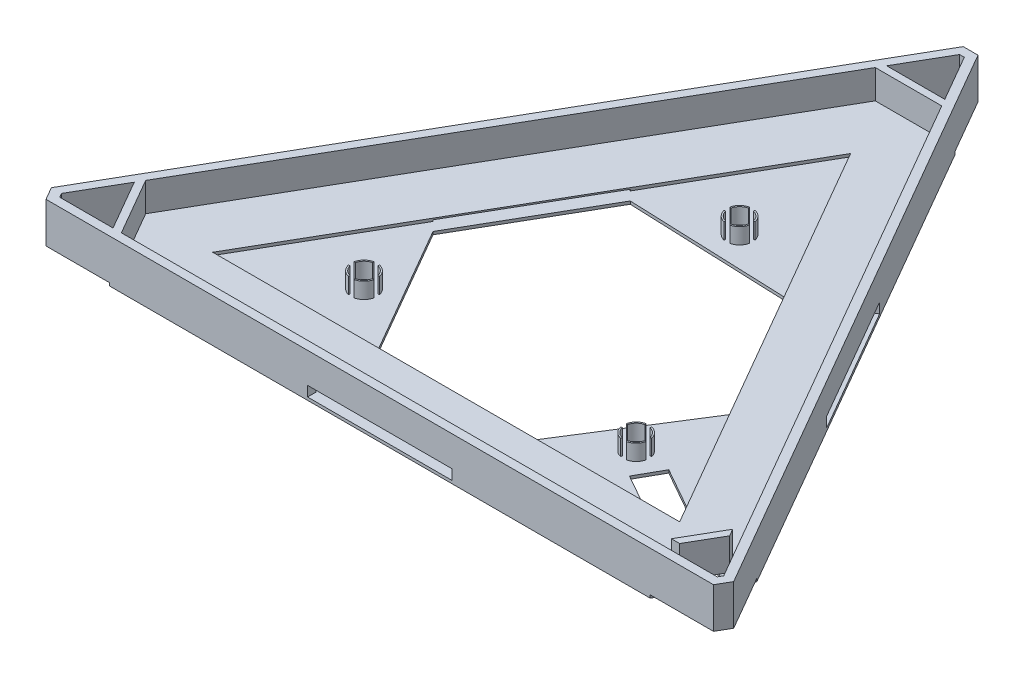
SolidWorks part; units mm, degrees
ref_plane "Front Plane" through (0, 0, 0) normal (0, 0, 1) x (1, 0, 0)
ref_plane "Top Plane" through (0, 0, 0) normal (0, 1, 0) x (1, 0, 0)
ref_plane "Right Plane" through (0, 0, 0) normal (1, 0, 0) x (0, 0, -1)
sketch "Sketch1" plane through (0, 0, 0) normal (0, 1, 0) x (1, 0, 0)
  line L0 (351.2729, 67.6655) -> (468.273, -134.9846)
  line L1 (347.2728, 67.6655) -> (347.2728, 65.1655) construction
  line L2 (409.773, -33.6595) -> (407.6079, -34.9095) construction
  line L3 (468.273, -134.9846) -> (464.2732, -141.9124)
  line L4 (230.2733, -141.9124) -> (464.2732, -141.9124)
  line L5 (230.2733, -141.9124) -> (226.2727, -134.9842)
  line L6 (226.2727, -134.9842) -> (343.2728, 67.6655)
  line L7 (353.4142, 63.9567) -> (351.2491, 62.7067) construction
  line L8 (347.2733, -141.9124) -> (347.2733, -139.4124) construction
  line L9 (231.7167, -139.4124) -> (462.8299, -139.4124)
  line L10 (284.7727, -33.6594) -> (286.9378, -34.9094) construction
  line L11 (344.7161, 65.1655) -> (349.8295, 65.1655)
  line L12 (465.3862, -134.9846) -> (349.8295, 65.1655)
  line L13 (466.2731, -138.4485) -> (464.1081, -137.1985) construction
  line L14 (462.8299, -139.4124) -> (465.3862, -134.9846)
  line L15 (229.1594, -134.9842) -> (344.7161, 65.1655)
  line L16 (229.1594, -134.9842) -> (231.7167, -139.4124)
  line L17 (286.9378, -34.9094) -> (287.3708, -35.1594) construction
  line L18 (230.438, -137.1983) -> (230.871, -136.9483) construction
  line L19 (232.0053, -138.9123) -> (229.7368, -134.9842)
  line L20 (343.2728, 67.6655) -> (351.2729, 67.6655)
  line L21 (345.0048, 64.6655) -> (229.7368, -134.9842)
  line L22 (349.5409, 64.6655) -> (345.0048, 64.6655)
  line L23 (249.0568, -126.4468) -> (246.8918, -127.697) construction
  line L24 (407.6079, -34.9095) -> (407.1749, -35.1595) construction
  line L26 (233.4463, -136.4089) -> (251.9226, -136.4093)
  line L27 (464.8089, -134.9846) -> (462.5412, -138.9123)
  line L28 (462.5412, -138.9123) -> (232.0053, -138.9123)
  line L29 (251.9226, -136.4093) -> (241.8609, -118.9847)
  line L30 (241.8609, -118.9847) -> (232.6236, -134.9842)
  line L31 (232.6236, -134.9842) -> (233.4463, -136.4089)
  line L33 (287.3708, -35.1594) -> (289.5359, -36.4094) construction
  line L34 (254.8093, -136.4089) -> (243.3042, -116.4848)
  line L35 (335.7675, 43.666) -> (243.3042, -116.4848)
  line L36 (358.7782, 43.666) -> (335.7675, 43.666)
  line L38 (289.5359, -36.4094) -> (306.8564, -46.4094) construction
  line L41 (461.939, -134.9846) -> (461.1164, -136.4093)
  line L42 (347.2688, -136.4172) -> (347.2688, -116.4172) construction
  line L43 (442.6021, -136.4093) -> (452.6999, -118.9847)
  line L44 (245.2636, -119.878) -> (249.0568, -126.4468) construction
  line L45 (452.6999, -118.9847) -> (461.939, -134.9846)
  line L48 (461.1164, -136.4093) -> (442.6021, -136.4093)
  line L49 (405.0134, -36.4027) -> (387.6936, -46.404) construction
  line L50 (306.8564, -46.4094) -> (466.2731, -138.4485) construction
  line L51 (357.3348, 46.166) -> (337.2109, 46.166)
  line L52 (337.2109, 46.166) -> (346.4484, 62.1659)
  line L53 (346.4484, 62.1659) -> (348.0966, 62.164)
  line L54 (348.0966, 62.164) -> (357.3348, 46.166)
  line L55 (228.273, -138.4483) -> (387.6936, -46.404) construction
  line L56 (347.2688, -116.4172) -> (347.2728, 43.666) construction
  line L57 (266.4391, -116.428) -> (428.1137, -116.4172)
  line L58 (347.2736, 23.6092) -> (428.1137, -116.4172)
  line L59 (266.4391, -116.428) -> (347.2736, 23.6092)
  line L60 (439.7283, -136.4254) -> (439.7283, -132.9254) construction
  line L61 (451.2487, -116.4715) -> (448.6507, -117.9717) construction
  line L62 (452.6999, -118.9847) -> (358.7782, 43.666)
  line L63 (442.6021, -136.4093) -> (254.8093, -136.4089)
  line L64 (441.749, -132.9254) -> (444.621, -132.9254)
  line L65 (448.6507, -117.9717) -> (450.9647, -121.979) construction
  line L66 (449.5167, -119.4714) -> (450.9647, -121.979)
  line L67 (441.749, -132.9254) -> (449.5167, -119.4714)
  line L68 (450.9647, -121.979) -> (444.621, -132.9254)
  point P13 (407.6079, -34.9095)
  point P20 (464.1081, -137.1985)
  point P23 (347.2733, -139.4124)
  point P25 (347.2732, -141.9124)
  point P27 (347.2728, 65.1655)
  point P31 (286.9378, -34.9094)
  point P37 (287.3708, -35.1594)
  point P39 (230.871, -136.9483)
  point P41 (347.2728, 64.6655)
  point P45 (407.1749, -35.1595)
  point P50 (246.8918, -127.697)
  point P56 (289.5359, -36.4094)
  point P58 (249.0568, -126.4468)
  point P60 (347.2728, 43.666)
  point P62 (345.0048, -136.4089)
  point P64 (445.4885, -126.4485)
  point P71 (447.651, -127.697)
  point P77 (347.2728, 46.166)
  point P84 (347.2688, -116.4172)
  point P87 (387.6936, -46.404)
  point P89 (306.8564, -46.4094)
  point P100 (405.0134, -36.4027)
  dimension "D1" = 2.5
  dimension "D2" = 2.5
  dimension "D3" = 2.5
  dimension "D4" = 2.5
  dimension "D5" = 2.5
  dimension "D6" = 2.5
  dimension "D7" = 0.5
  dimension "D8" = 0.5
  dimension "D9" = 0.5
  dimension "D10" = 2.5
  dimension "D11" = 2.5
  dimension "D12" = 20
  dimension "D13" = 20
  dimension "D14" = 20
  dimension "D15" = 3.5
  dimension "D16" = 3
extrude "Boss-Extrude1" add sketch "Sketch1" along normal blind 1 contours L36 L35 L34 L57 L59 L58 region at (251.4484, 0, 125.0658)
extrude "Boss-Extrude2" add sketch "Sketch1<9>" along normal blind 11 contours L28 L27 L22 L21 L19 L31 L30 L29 L26 L34 L35 L36 L41 L48 L43 L45 L53 L54 L51 L52 | L68 L64 L67 L66 region at (230.7087, 0, 137.042)
sketch "Sketch1<9>" plane through (0, 0, 0) normal (0, 1, 0) x (1, 0, 0) same geometry as "Sketch1"
extrude "Boss-Extrude3" add sketch "Sketch1<10>" along normal blind 5 and the other way blind 3 contours L28 L27 L22 L21 L19 L31 L30 L29 L26 L34 L35 L36 L41 L48 L43 L45 L53 L54 L51 L52 region at (230.7087, 0, 137.042)
sketch "Sketch1<10>" plane through (0, 0, 0) normal (0, 1, 0) x (1, 0, 0) same geometry as "Sketch1"
sketch "Sketch3" plane through (290.5896, 0, -167.772) normal (0.866, 0, -0.5) x (-0.5, 0, -0.866)
  line L1 (-261.593, -6.5) -> (-211.593, -6.5)
  line L2 (-261.593, -6.5) -> (-261.593, 0.5)
  line L3 (-261.593, 0.5) -> (-211.593, 0.5)
  line L4 (-211.593, -6.5) -> (-211.593, 0.5)
  line L5 (-261.593, -6.5) -> (-211.593, 0.5) construction
  line L6 (-261.593, 0.5) -> (-211.593, -6.5) construction
  point P0 (-236.593, -3)
  dimension "D1" = 50
  dimension "D2" = 7
extrude "Cut-Extrude3" cut sketch "Sketch3" against normal blind 25
sketch "Sketch5" plane through (0, 0, 139.4124) normal (0, 0, 1) x (1, 0, 0)
  line L0 (231.7167, -3) -> (462.8299, -3) construction
  line L1 (322.2733, -6.5) -> (372.2733, -6.5)
  line L2 (322.2733, -6.5) -> (322.2733, 0.5)
  line L3 (322.2733, 0.5) -> (372.2733, 0.5)
  line L4 (372.2733, -6.5) -> (372.2733, 0.5)
  line L5 (322.2733, -6.5) -> (372.2733, 0.5) construction
  line L6 (322.2733, 0.5) -> (372.2733, -6.5) construction
  point P0 (347.2733, -3)
  dimension "D1" = 50
  dimension "D2" = 7
extrude "Cut-Extrude4" cut sketch "Sketch5" against normal blind 25
sketch "Sketch6" plane through (230.3194, 0, 132.9752) normal (-0.866, 0, -0.5) x (-0.5, 0, 0.866)
  line L0 (2.3199, -3) -> (-228.7932, -3) construction
  line L1 (-138.2367, -6.5) -> (-88.2367, -6.5)
  line L2 (-138.2367, -6.5) -> (-138.2367, 0.5)
  line L3 (-138.2367, 0.5) -> (-88.2367, 0.5)
  line L4 (-88.2367, -6.5) -> (-88.2367, 0.5)
  line L5 (-138.2367, -6.5) -> (-88.2367, 0.5) construction
  line L6 (-138.2367, 0.5) -> (-88.2367, -6.5) construction
  point P0 (-113.2367, -3)
  dimension "D1" = 50
  dimension "D2" = 7
extrude "Cut-Extrude5" cut sketch "Sketch6" against normal blind 25
sketch "Sketch8" plane through (0, -3, 0) normal (0, -1, 0) x (1, 0, 0)
  line L0 (246.8918, 127.697) -> (257.9651, 146.8734) construction
  line L1 (251.9226, 136.4093) -> (241.8609, 118.9847) construction
  line L2 (447.651, 127.697) -> (454.4275, 116.0035) construction
  line L3 (442.6021, 136.4093) -> (452.6999, 118.9847) construction
  line L4 (465.3862, 134.9846) -> (421.3861, 58.7742) construction
  line L5 (347.2728, -46.166) -> (333.7468, -46.166) construction
  line L6 (357.3348, -46.166) -> (337.2109, -46.166) construction
  line L7 (299.4378, 13.2587) -> (344.7161, -65.1655) construction
  line L8 (246.8918, 127.697) -> (240.1287, 115.9849)
  line L9 (229.1594, 134.9842) -> (274.4378, 56.56) construction
  line L10 (240.1287, 115.9849) -> (333.7468, -46.166)
  line L11 (333.7468, -46.166) -> (360.7989, -46.166)
  line L12 (396.3861, 15.4729) -> (349.8295, -65.1655) construction
  line L13 (360.7989, -46.166) -> (454.4275, 116.0035)
  line L15 (372.2733, 139.4124) -> (462.8299, 139.4124) construction
  line L16 (440.9124, 139.4124) -> (253.6568, 139.4124)
  line L17 (231.7167, 139.4124) -> (322.2733, 139.4124) construction
  line L18 (253.6568, 139.4124) -> (246.8918, 127.697)
  line L19 (322.2733, 116.4243) -> (294.3582, 68.0611)
  line L20 (294.3582, 68.0611) -> (319.3545, 24.7577)
  line L21 (319.3545, 24.7577) -> (376.4737, 26.9694)
  line L22 (376.4737, 26.9694) -> (401.4727, 70.2712)
  line L23 (401.4727, 70.2712) -> (372.2733, 116.4209)
  line L24 (372.2733, 116.4209) -> (322.2733, 116.4243)
  line L25 (386.873, 93.3461) -> (395.3235, 98.6928) construction
  line L30 (308.3157, 92.2427) -> (299.6549, 97.2417) construction
  line L31 (347.9141, 25.8635) -> (348.3013, 15.8635) construction
  line L32 (440.9124, 139.4124) -> (445.2267, 131.9864)
  line L33 (454.4275, 116.0035) -> (450.147, 123.2807)
  line L34 (401.698, 107.3846) -> (445.2267, 131.9864)
  line L35 (450.147, 123.2807) -> (406.6183, 98.6788)
  line L36 (401.698, 107.3846) -> (406.6183, 98.6788)
  circle A0 centre (395.3235, 98.6928) radius 1.5
  circle A1 centre (348.3013, 15.8635) radius 1.5
  circle A2 centre (299.6549, 97.2417) radius 1.5
  dimension "D6" = 3
  dimension "D7" = 3
  dimension "D8" = 3
  dimension "D1" = 10
  dimension "D2" = 50
  dimension "D3" = 10
  dimension "D4" = 10
  dimension "D5" = 10
extrude "Boss-Extrude5" add sketch "Sketch8" along normal blind 1
sketch "Sketch12" plane through (0, -3, 0) normal (0, 1, 0) x (1, 0, 0)
  line L0 (348.3013, -11.8635) -> (348.3013, -11.3635) construction
  line L1 (348.3013, -11.3635) -> (349.2951, -11.4746) construction
  line L2 (349.2951, -11.4746) -> (349.1847, -11.9623)
  line L3 (348.3013, -11.3635) -> (347.3075, -11.4746) construction
  line L4 (347.3075, -11.4746) -> (347.4179, -11.9623)
  line L5 (352.3013, -15.8635) -> (352.8013, -15.8635) construction
  line L6 (344.3013, -15.8635) -> (343.8013, -15.8635) construction
  line L7 (348.3013, -19.8635) -> (348.3013, -20.3635) construction
  line L8 (352.8013, -15.8635) -> (352.6902, -14.8697) construction
  line L9 (352.8013, -15.8635) -> (352.6902, -16.8573) construction
  line L10 (343.8013, -15.8635) -> (343.9124, -14.8697) construction
  line L11 (343.8013, -15.8635) -> (343.9124, -16.8573) construction
  line L12 (348.3013, -20.3635) -> (349.2951, -20.2524) construction
  line L13 (348.3013, -20.3635) -> (347.3075, -20.2524) construction
  line L14 (343.9124, -14.8697) -> (348.3013, -15.8635) construction
  line L15 (348.3013, -15.8635) -> (352.6902, -14.8697) construction
  line L16 (343.9124, -16.8573) -> (348.3013, -15.8635) construction
  line L17 (348.3013, -15.8635) -> (352.6902, -16.8573) construction
  line L18 (347.3075, -20.2524) -> (348.3013, -15.8635) construction
  line L19 (348.3013, -15.8635) -> (349.2951, -20.2524) construction
  line L20 (343.9124, -14.8697) -> (344.4001, -14.9801)
  line L21 (343.9124, -16.8573) -> (344.4001, -16.7469)
  line L22 (347.3075, -20.2524) -> (347.4179, -19.7648)
  line L23 (349.2951, -20.2524) -> (349.1847, -19.7648)
  line L24 (352.6902, -14.8697) -> (352.2025, -14.9801)
  line L25 (352.6902, -16.8573) -> (352.2025, -16.7469)
  line L26 (395.3235, -94.1928) -> (395.3235, -98.6928) construction
  line L27 (395.3235, -98.6928) -> (390.8235, -98.6928) construction
  line L28 (390.8235, -98.6928) -> (390.9347, -97.699) construction
  line L29 (399.8235, -98.6928) -> (395.3235, -98.6928) construction
  line L30 (395.3235, -98.6928) -> (395.3235, -103.1928) construction
  line L31 (395.3235, -103.1928) -> (396.3173, -103.0817) construction
  line L32 (395.3235, -94.1928) -> (396.3173, -94.3039) construction
  line L33 (395.3235, -94.1928) -> (394.3297, -94.3039) construction
  line L34 (399.7124, -97.699) -> (399.8235, -98.6928) construction
  line L35 (399.8235, -98.6928) -> (399.7124, -99.6866) construction
  line L36 (390.9347, -99.6866) -> (390.8235, -98.6928) construction
  line L37 (394.3297, -103.0817) -> (395.3235, -103.1928) construction
  line L38 (394.3297, -94.3039) -> (395.3235, -98.6928) construction
  line L39 (395.3235, -98.6928) -> (396.3173, -94.3039) construction
  line L40 (390.9347, -99.6866) -> (395.3235, -98.6928) construction
  line L41 (395.3235, -98.6928) -> (390.9347, -97.699) construction
  line L42 (399.7124, -97.699) -> (395.3235, -98.6928) construction
  line L43 (395.3235, -98.6928) -> (399.7124, -99.6866) construction
  line L44 (394.3297, -103.0817) -> (395.3235, -98.6928) construction
  line L45 (395.3235, -98.6928) -> (396.3173, -103.0817) construction
  line L46 (394.3297, -94.3039) -> (394.4402, -94.7916)
  line L47 (396.3173, -94.3039) -> (396.2069, -94.7916)
  line L48 (399.7124, -97.699) -> (399.2248, -97.8094)
  line L49 (399.7124, -99.6866) -> (399.2248, -99.5762)
  line L50 (396.3173, -103.0817) -> (396.2069, -102.5941)
  line L51 (394.3297, -103.0817) -> (394.4402, -102.5941)
  line L52 (390.9347, -99.6866) -> (391.4223, -99.5762)
  line L53 (390.9347, -97.699) -> (391.4248, -97.7985)
  line L54 (299.6549, -92.7417) -> (299.6549, -97.2417) construction
  line L55 (299.6549, -97.2417) -> (304.1549, -97.2417) construction
  line L56 (299.6549, -101.7417) -> (299.6549, -97.2417) construction
  line L57 (299.6549, -97.2417) -> (295.1549, -97.2417) construction
  line L58 (299.6549, -97.2417) -> (298.6611, -92.8528) construction
  line L59 (298.6611, -92.8528) -> (299.6549, -92.7417) construction
  line L60 (299.6549, -92.7417) -> (300.6487, -92.8528) construction
  line L61 (300.6487, -92.8528) -> (299.6549, -97.2417) construction
  line L62 (299.6549, -97.2417) -> (304.0438, -96.2479) construction
  line L63 (304.0438, -96.2479) -> (304.1549, -97.2417) construction
  line L64 (304.1549, -97.2417) -> (304.0438, -98.2355) construction
  line L65 (304.0438, -98.2355) -> (299.6549, -97.2417) construction
  line L66 (299.6549, -97.2417) -> (300.6487, -101.6306) construction
  line L67 (300.6487, -101.6306) -> (299.6549, -101.7417) construction
  line L68 (299.6549, -101.7417) -> (298.6611, -101.6306) construction
  line L69 (298.6611, -101.6306) -> (299.6549, -97.2417) construction
  line L70 (299.6549, -97.2417) -> (295.266, -98.2355) construction
  line L71 (295.266, -98.2355) -> (295.1549, -97.2417) construction
  line L72 (295.1549, -97.2417) -> (295.266, -96.2479) construction
  line L73 (295.266, -96.2479) -> (299.6549, -97.2417) construction
  line L74 (295.266, -96.2479) -> (295.7537, -96.3583)
  line L75 (295.266, -98.2355) -> (295.7537, -98.1251)
  line L76 (298.6611, -101.6306) -> (298.7715, -101.1429)
  line L77 (300.6487, -101.6306) -> (300.5383, -101.1429)
  line L78 (304.0438, -98.2355) -> (303.5561, -98.1251)
  line L79 (304.0438, -96.2479) -> (303.5561, -96.3583)
  line L80 (300.6487, -92.8528) -> (300.5383, -93.3404)
  line L81 (298.6611, -92.8528) -> (298.7715, -93.3404)
  circle A0 centre (348.3013, -15.8635) radius 4.5
  circle A1 centre (395.3235, -98.6928) radius 4.5
  circle A2 centre (299.6549, -97.2417) radius 4.5
  circle A3 centre (348.3013, -15.8635) radius 4
  circle A4 centre (395.3235, -98.6928) radius 4
  circle A5 centre (299.6549, -97.2417) radius 4
  dimension "D1" = 9
  dimension "D2" = 9
  dimension "D3" = 9
  dimension "D4" = 8
  dimension "D5" = 8
  dimension "D6" = 8
  dimension "D7" = 1
  dimension "D8" = 1
  dimension "D9" = 1
  dimension "D10" = 1
  dimension "D11" = 1
  dimension "D12" = 1
  dimension "D13" = 1
  dimension "D14" = 1
  dimension "D15" = 1
  dimension "D16" = 1
  dimension "D17" = 1
  dimension "D18" = 1
  dimension "D19" = 1
  dimension "D20" = 1
  dimension "D21" = 1
  dimension "D22" = 1
  dimension "D23" = 1
  dimension "D24" = 1
  dimension "D25" = 1
  dimension "D26" = 1
  dimension "D27" = 1
  dimension "D28" = 1
  dimension "D29" = 1
  dimension "D30" = 1
extrude "Boss-Extrude10" add sketch "Sketch12" along normal blind 5.5 contours A3 L4 A0 L20 | A3 L24 A0 L2 | A3 L23 A0 L25 | A3 L21 A0 L22 | A4 L46 A1 L53 | A4 L48 A1 L47 | A4 L50 A1 L49 | A4 L52 A1 L51 | A5 L81 A2 L74 | A5 L79 A2 L80 | A5 L77 A2 L78 | A5 L75 A2 L76 region at (351.1537, -3, 13.0111) region at (345.4489, -3, 13.0111) region at (351.1537, -3, 18.7159) region at (345.4489, -3, 18.7159) region at (392.4726, -3, 95.8382) region at (398.1759, -3, 95.8404) region at (392.4712, -3, 101.5452) region at (398.1759, -3, 101.5452) region at (296.8025, -3, 94.3893) region at (296.8025, -3, 100.0941) region at (302.5073, -3, 94.3893) region at (302.5073, -3, 100.0941)
